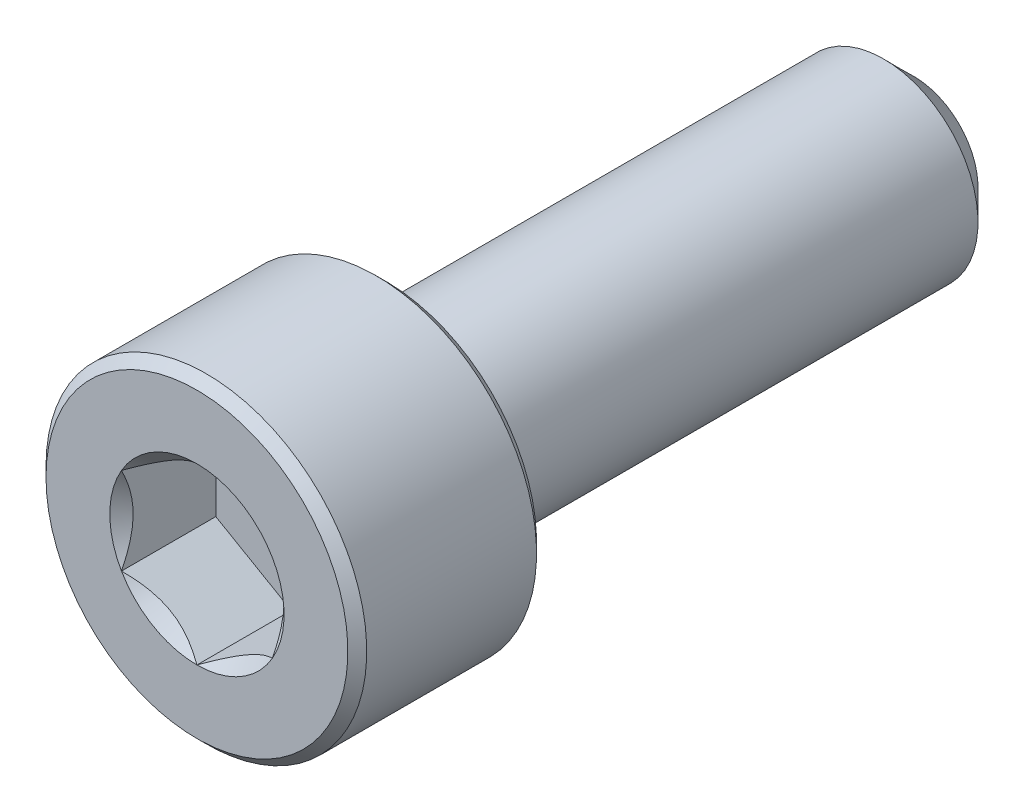
SolidWorks part; units mm, degrees
ref_plane "Front Plane" through (0, 0, 0) normal (0, 0, 1) x (1, 0, 0)
ref_plane "Top Plane" through (0, 0, 0) normal (0, 1, 0) x (1, 0, 0)
ref_plane "Right Plane" through (0, 0, 0) normal (1, 0, 0) x (0, 0, -1)
sketch "Sketch1" plane through (0, 0, 0) normal (1, 0, 0) x (0, 0, -1)
  line L0 (-9.5, 0) -> (9.5, 0) construction
  line L1 (9.5, 0) -> (9.5, 1.7) construction
  line L2 (9.5, 1.7) -> (8.7, 2.5) construction
  line L3 (8.7, 2.5) -> (-4.5, 2.5) construction
  line L5 (-4.5, 2.5) -> (-4.5, 4.25) construction
  line L6 (-4.5, 4.25) -> (-9.5, 4.25) construction
  line L7 (-9.5, 4.25) -> (-9.5, 0) construction
  line L8 (9.5, 1.7) -> (9.5, 2.5) construction
  line L9 (9.45, 2.5866) -> (9.85, 1.8938) construction
  line L10 (9.85, 1.8938) -> (10.25, 2.5866) construction
  line L11 (10.25, 2.5866) -> (9.45, 2.5866) construction
  line L12 (9.85, 2.5866) -> (9.85, 2.5) construction
  line L13 (9.85, 1.8938) -> (9.85, 1.9804) construction
  line L14 (9.8, 1.9804) -> (9.9, 1.9804) construction
  line L15 (9.5, 2.5) -> (10.2, 2.5) construction
  line L16 (9.475, 2.5433) -> (10.225, 2.5433) construction
  line L17 (9.5, 0) -> (9.5, -2.5) construction
  line L18 (-4.75, 4.25) -> (-4.5, 4) construction
  line L19 (-9.25, 4.25) -> (-9.5, 4) construction
  point P0 (-9.5, 2)
  point P3 (6.7, 2.5)
  point P4 (0, 0)
  point P22 (9.85, 1.9804)
  point P24 (-4.5, 2.5)
  point P25 (9.85, 2.5)
  point P28 (9.85, 2.5433)
  point P29 (6.7, -2.5)
  point P31 (-7, 4.25)
  point P37 (-5.375, 4.25)
  point P38 (-9.125, 4.25)
  point P41 (-7, 0)
  dimension "head height" = 5
  dimension "D1" = 45
  dimension "Head Diameter" = 8.5
  dimension "Thread Size" = 5
  dimension "drive size" = 4
  dimension "Thread Pitch" = 0.8
  dimension "D2" = 0.1
  dimension "D3" = 0.8
  dimension "D4" = 2.8
  dimension "D7" = 0.25
  dimension "D8" = 0.25
  dimension "D9" = 0.25
  dimension "D10" = 0.125
  dimension "D11" = 0.625
  dimension "length" = 14
  dimension "Drive Depth" = 2.5
sketch "Sketch2" plane through (0, 0, 0) normal (1, 0, 0) x (0, 0, -1)
  line L1 (-9.25, 4.25) -> (-4.75, 4.25)
  line L4 (8.7, 2.5) -> (9.5, 1.7)
  line L5 (9.5, 1.7) -> (9.5, 0)
  line L6 (-4.75, 4.25) -> (-4.5, 4) construction
  line L7 (9.5, 0) -> (-9.5, 0)
  line L8 (-9.25, 4.25) -> (-9.5, 4) construction
  line L9 (-4.75, 4.25) -> (-4.5, 4)
  line L10 (-9.25, 4.25) -> (-9.5, 4)
  line L11 (-9.5, 4) -> (-9.5, 0)
  line L12 (-4.5, 4) -> (-4.5, 2.5)
  line L13 (-4.5, 2.5) -> (8.7, 2.5)
revolve "Revolve1" add sketch "Sketch2" angle 360 about L7
sketch "Sketch3" plane through (0, 0, 9.5) normal (0, 0, 1) x (1, 0, 0)
  line L1 (0, 2.3094) -> (-2, 1.1547)
  line L2 (-2, 1.1547) -> (-2, -1.1547)
  line L3 (-2, -1.1547) -> (0, -2.3094)
  line L4 (0, -2.3094) -> (2, -1.1547)
  line L5 (2, -1.1547) -> (2, 1.1547)
  line L6 (2, 1.1547) -> (0, 2.3094)
  circle A0 centre (0, 0) radius 2 construction
  dimension "D1" = 4
extrude "Cut-Extrude1" cut sketch "Sketch3" against normal up to vertex (2.5 mm away) up to point (0, 0, 7)
sketch "Sketch4" plane through (0, 0, 9.5) normal (0, 0, 1) x (1, 0, 0)
  circle A0 centre (0, 0) radius 2.3094
extrude "Cut-Extrude2" cut sketch "Sketch4" against normal blind 0.5 draft 45
ref_plane "Plane1" [suppressed] through (0, 0, 4.5) normal (0, 0, 1) x (1, 0, 0)
split "Split1" [suppressed] bodies to split 106
sketch "Sketch6" [suppressed] plane through (0, 0, -9.5) normal (0, 0, -1) x (-1, 0, 0)
  circle A0 centre (0, 0) radius 2.5
curve "Helix/Spiral1" [suppressed] pitch 0.8 height 14.8 turns 18.5
sketch "Sketch7" [suppressed] plane through (0, 0, 0) normal (1, 0, 0) x (0, 0, -1)
  line L0 (9.475, 2.5433) -> (10.225, 2.5433)
  line L1 (10.225, 2.5433) -> (9.9, 1.9804)
  line L2 (9.9, 1.9804) -> (9.8, 1.9804)
  line L3 (9.8, 1.9804) -> (9.475, 2.5433)
sweep "Cut-Sweep1" [suppressed] cut profiles "Sketch7" path "Helix/Spiral1"
sketch "Sketch8" [suppressed] plane through (0, 0, 4.5) normal (0, 0, -1) x (-1, 0, 0)
  circle A0 centre (0, 0) radius 2.5
extrude "Boss-Extrude1" [suppressed] add sketch "Sketch8" along normal through all draft 45
ref_plane "Plane2" [suppressed] through (0, 0, 7) normal (0, 0, 1) x (1, 0, 0)
sketch "Sketch9" [suppressed] plane through (0, 0, 7) normal (0, 0, 1) x (1, 0, 0)
  line L0 (0, 4.1331) -> (0.1113, 4.2485)
  line L1 (0, 4.1331) -> (-0.1113, 4.2485)
  line L2 (0, 4.25) -> (0, 0) construction
  line L3 (-0.1113, 4.2485) -> (0, 0) construction
  line L4 (0, 0) -> (0.1113, 4.2485) construction
  arc A0 (0.1113, 4.2485) -> (-0.1113, 4.2485) centre (0, 0) ccw
  circle A1 centre (0, 0) radius 4.1331 construction
  dimension "D1" = 8.5
  dimension "D2" = 8.2662
  dimension "D3" = 3
extrude "Cut-Extrude4" [suppressed] cut sketch "Sketch9" against normal up to vertex and the other way up to vertex
pattern_circular "CirPattern2" [suppressed] count 96 over 360 about axis through (0, 0, 9.5) along (0, 0, -1) of bodies 113
equation "\"D2@Sketch1\" = \"Thread Pitch@Sketch1\" / 8"
equation "\"D3@Sketch1\" = \"Thread Pitch@Sketch1\""
equation "\"D3@Helix/Spiral1\" = \"length@Sketch1\" + \"Thread Pitch@Sketch1\""
equation "\"D4@Helix/Spiral1\" = \"Thread Pitch@Sketch1\""
equation "\"D4@Sketch1\" = \"Thread Pitch@Sketch1\" * 3.5"
equation "\"D7@Sketch1\"=\"head height@Sketch1\"*.05"
equation "\"D8@Sketch1\"=\"D7@Sketch1\""
equation "\"D9@Sketch1\"=\"D7@Sketch1\""
equation "\"D10@Sketch1\"=\"D7@Sketch1\"/2"
equation "\"D11@Sketch1\"=\"D10@Sketch1\"*5"
equation "\"D1@CirPattern2\"=( 360 / \"D3@Sketch9\" )*0.8"
equation "\"D1@Sketch3\" = \"drive size@Sketch1\""
equation "\"D2@Sketch9\"=\"Head Diameter@Sketch1\" * 0.9725"
